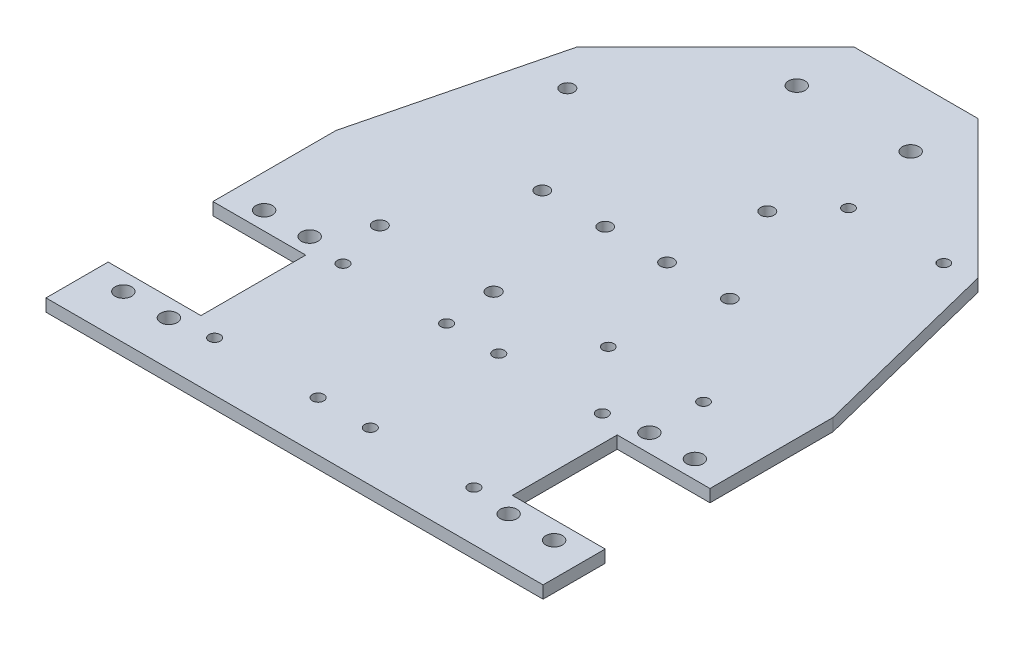
SolidWorks part; units mm, degrees
ref_plane "Front Plane" through (0, 0, 0) normal (0, 0, 1) x (1, 0, 0)
ref_plane "Top Plane" through (0, 0, 0) normal (0, 1, 0) x (1, 0, 0)
ref_plane "Right Plane" through (0, 0, 0) normal (1, 0, 0) x (0, 0, -1)
sketch "Sketch1" plane through (0, 0, 0) normal (0, 1, 0) x (1, 0, 0)
  line L0 (-60, 0) -> (60, 0)
  line L1 (-60, 0) -> (-60, 150)
  line L2 (-60, 150) -> (60, 150)
  line L3 (60, 150) -> (60, 0)
  line L4 (0, 0) -> (0, 68.7278) construction
  line L5 (60, 70) -> (40, 150)
  line L6 (-60, 70) -> (-40, 150)
  line L8 (-60, 15) -> (-37.6, 15)
  line L9 (60, 15) -> (37.6, 15)
  line L10 (60, 15) -> (60, 40.3)
  line L11 (60, 40.3) -> (37.6, 40.3)
  line L12 (37.6, 15) -> (37.6, 40.3)
  line L13 (-60, 15) -> (-60, 40.3)
  line L14 (-60, 40.3) -> (-37.6, 40.3)
  line L15 (-37.6, 15) -> (-37.6, 40.3)
  point P4 (0, 0)
  dimension "D1" = 40
  dimension "D2" = 40
  dimension "D3" = 120
  dimension "D4" = 150
  dimension "D5" = 70
  dimension "D6" = 70
  dimension "D7" = 15
  dimension "D8" = 15
  dimension "D9" = 25.3
  dimension "D10" = 25.3
  dimension "D11" = 22.4
  dimension "D12" = 22.4
extrude "Boss-Extrude1" add sketch "Sketch1" along normal blind 3 contours L15 L8 L1 L0 L3 L9 L12 L11 L5 L2 L6 L14 region at (0, 0, -73.4499)
sketch "Sketch2" plane through (0, 3, 0) normal (0, 1, 0) x (1, 0, 0)
  line L0 (6.3, 12) -> (31.3, 12) construction
  line L5 (-31.3, 12) -> (-6.3, 12) construction
  line L6 (-31.3, 12) -> (-31.3, 43) construction
  line L7 (-31.3, 43) -> (-6.3, 43) construction
  line L8 (-6.3, 12) -> (-6.3, 43) construction
  line L9 (6.3, 12) -> (6.3, 43) construction
  line L10 (6.3, 43) -> (31.3, 43) construction
  line L11 (31.3, 12) -> (31.3, 43) construction
  line L12 (0, 0) -> (0, 150) construction
  line L13 (-40, 150) -> (40, 150) construction
  line L14 (-60, 0) -> (60, 0) construction
  line L15 (-37.6, 15) -> (-37.6, 40.3) construction
  line L16 (37.6, 15) -> (37.6, 40.3) construction
  circle A0 centre (-31.3, 43) radius 1.375
  circle A1 centre (-6.3, 43) radius 1.375
  circle A2 centre (-6.3, 12) radius 1.375
  circle A3 centre (-31.3, 12) radius 1.375
  circle A4 centre (6.3, 43) radius 1.375
  circle A5 centre (31.3, 43) radius 1.375
  circle A6 centre (31.3, 12) radius 1.375
  circle A7 centre (6.3, 12) radius 1.375
  dimension "D3" = 25
  dimension "D9" = 2.75
  dimension "D10" = 2.75
  dimension "D11" = 2.75
  dimension "D12" = 2.75
  dimension "D13" = 2.75
  dimension "D14" = 2.75
  dimension "D15" = 2.75
  dimension "D16" = 2.75
  dimension "D1" = 25
  dimension "D2" = 31
  dimension "D4" = 31
  dimension "D5" = 12
  dimension "D6" = 12
  dimension "D7" = 6.3
  dimension "D8" = 6.3
sketch "Sketch4" plane through (0, 3, 0) normal (0, 1, 0) x (1, 0, 0)
  circle A2 centre (-22.548, 82.3665) radius 1.6086
  circle A4 centre (-7.3727, 82.375) radius 1.6
  circle A5 centre (22.7264, 82.3751) radius 1.6
  circle A6 centre (7.5498, 82.375) radius 1.6
extrude "Cut-Extrude1" cut sketch "Sketch2" against normal blind 10 and the other way blind 10
extrude "Cut-Extrude2" cut sketch "Sketch4" against normal blind 10 and the other way blind 10
sketch "Sketch5" plane through (0, 3, 0) normal (0, 1, 0) x (1, 0, 0)
  line L0 (-51.9886, 44.6489) -> (-51.9886, 44.6494) construction
  circle A0 centre (-51.9886, 44.6489) radius 2
  circle A1 centre (-40.9886, 44.6489) radius 2
  circle A2 centre (-51.9886, 10.6598) radius 2
  circle A3 centre (-40.9886, 10.6598) radius 2
  circle A4 centre (41.0114, 10.6598) radius 2
  circle A5 centre (52.0114, 10.6598) radius 2
  circle A6 centre (52.0114, 44.6489) radius 2
  circle A7 centre (41.0113, 44.6521) radius 1.9969
extrude "Cut-Extrude3" cut sketch "Sketch5" against normal blind 5 and the other way blind 5
chamfer "Chamfer1" distance 25 angle 45 2 edges at (-40, 1.5, -150) (40, 1.5, -150) first distance on face at (0, 1.5, -150)
sketch "Sketch6" plane through (0, 3, 0) normal (0, 1, 0) x (1, 0, 0)
  circle A0 centre (-40.9004, 106.7526) radius 1.632
  circle A1 centre (8.9618, 105.165) radius 1.6212
  circle A2 centre (-7.264, 55.3195) radius 1.6515
  circle A3 centre (-34.8627, 55.4422) radius 1.6263
extrude "Cut-Extrude4" cut sketch "Sketch6" against normal blind 10 and the other way blind 10
sketch "Sketch7" plane through (0, 3, 0) normal (0, 1, 0) x (1, 0, 0)
  circle A0 centre (18.097, 115.6421) radius 1.35
  circle A1 centre (41.097, 115.6421) radius 1.35
  circle A2 centre (18.097, 57.6421) radius 1.35
  circle A3 centre (41.097, 57.6421) radius 1.35
extrude "Cut-Extrude5" cut sketch "Sketch7" against normal blind 10 and the other way blind 10
sketch "Sketch8" plane through (0, 0, 0) normal (0, -1, 0) x (1, 0, 0)
  line L0 (-13.75, -135) -> (13.75, -135) construction
  line L1 (0, -150) -> (0, -135) construction
  line L2 (-15, -150) -> (15, -150) construction
  circle A0 centre (13.75, -135) radius 2
  circle A1 centre (-13.75, -135) radius 2
  point P3 (0, -135)
extrude "Cut-Extrude6" cut sketch "Sketch8" against normal blind 10 and the other way blind 10 contours A1 | A0
